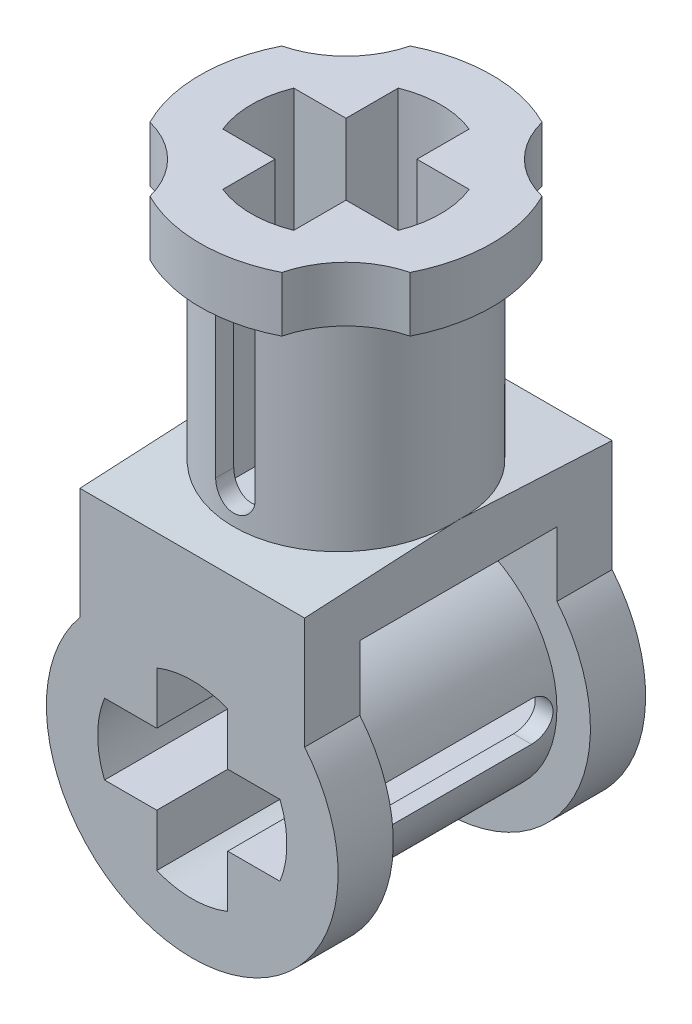
SolidWorks part; units mm, degrees
ref_plane "Front Plane" through (0, 0, 0) normal (0, 0, 1) x (1, 0, 0)
ref_plane "Top Plane" through (0, 0, 0) normal (0, 1, 0) x (1, 0, 0)
ref_plane "Right Plane" through (0, 0, 0) normal (1, 0, 0) x (0, 0, -1)
sketch "Sketch1" plane through (0, 0, 0) normal (0, 1, 0) x (1, 0, 0)
  circle A0 centre (0, 0) radius 2.85
  dimension "D1" = 5.7
extrude "Middle Body" add sketch "Sketch1" along normal mid plane 5.1
sketch "Sketch2" plane through (0, -2.55, 0) normal (0, -1, 0) x (1, 0, 0)
  circle A0 centre (0, 0) radius 3.7
  dimension "D1" = 7.4
extrude "Outer Rim" add sketch "Sketch2" along normal blind 1.4
mirror "Mirror1" about plane through (0, 0, 0) normal (0, 1, 0) of "Outer Rim"
sketch "Sketch3" plane through (0, 0, 0) normal (0, 1, 0) x (1, 0, 0)
  line L1 (2.4, -0.9) -> (-2.4, -0.9)
  line L2 (2.4, -0.9) -> (2.4, 0.9)
  line L3 (2.4, 0.9) -> (-2.4, 0.9)
  line L4 (-2.4, -0.9) -> (-2.4, 0.9)
  line L5 (2.4, -0.9) -> (-2.4, 0.9) construction
  line L6 (2.4, 0.9) -> (-2.4, -0.9) construction
  line L7 (0.9, -2.4) -> (-0.9, -2.4)
  line L8 (0.9, -2.4) -> (0.9, 2.4)
  line L9 (0.9, 2.4) -> (-0.9, 2.4)
  line L10 (-0.9, -2.4) -> (-0.9, 2.4)
  line L11 (0.9, -2.4) -> (-0.9, 2.4) construction
  line L12 (0.9, 2.4) -> (-0.9, -2.4) construction
  circle A0 centre (0, 0) radius 2.4
  dimension "D1" = 4.8
  dimension "D2" = 1.8
extrude "Axle Cut" cut sketch "Sketch3" against normal through all both and the other way through all contours L8 A0 L10 L3 | L3 A0 L1 L10 | L10 L1 L8 L3 | A0 L8 L1 L10 | L1 A0 L3 L8 region at (1.6222, 0, 0) region at (0, 0, 1.6222) region at (0, 0, 0) region at (-1.6222, 0, 0) region at (0, 0, -1.6222)
sketch "Sketch4" plane through (0, 0, 0) normal (0, 0, 1) x (1, 0, 0)
  line L0 (0, -1.9) -> (0, 1.9) construction
  line L1 (-0.5, -1.9) -> (-0.5, 1.9)
  line L2 (0.5, -1.9) -> (0.5, 1.9)
  arc A0 (-0.5, -1.9) -> (0.5, -1.9) centre (0, -1.9) ccw
  arc A1 (0.5, 1.9) -> (-0.5, 1.9) centre (0, 1.9) ccw
  point P2 (0, 0)
  dimension "D2" = 4.8
  dimension "D1" = 1
extrude "Slot Cut" cut sketch "Sketch4" against normal through all both and the other way through all
sketch "Sketch5" plane through (0, 3.95, 0) normal (0, 1, 0) x (1, 0, 0)
  line L0 (0, 0) -> (3.8509, 3.8509) construction
  line L2 (0.9, 0.9) -> (0.9, 2.2249) construction
  circle A0 centre (0, 0) radius 3.2
  circle A3 centre (3.8509, 3.8509) radius 2.246
  circle A4 centre (0, 0) radius 3.7 construction
  circle A5 centre (3.8509, -3.8509) radius 2.246
  circle A6 centre (-3.8509, -3.8509) radius 2.246
  circle A7 centre (-3.8509, 3.8509) radius 2.246
  point P7 (1.6735, 3.2999)
  point P8 (3.2999, 1.6735)
  circle M23 centre (0, 0) radius 3.7
  dimension "D1" = 6.4
  dimension "D3" = 2.3
  dimension "D2" = 45
  dimension "D4" = 4
extrude "Scallop Cut " cut sketch "Sketch5" against normal blind 1.4 contours A7 M23 | L0 A3 M23 | A3 L0 M23 | A5 | A6 region at (2.141, 3.95, -2.7556) region at (2.7556, 3.95, -2.141) region at (-2.4483, 3.95, -2.4483)
sketch "Sketch6" plane through (0, 0, 0) normal (0, 0, 1) x (1, 0, 0)
  line L0 (1.6735, 3.95) -> (-1.6735, 3.95) construction
  circle A0 centre (0, -7.95) radius 2.85
  dimension "D1" = 5.7
  dimension "D2" = 11.9
extrude "Middle Top " add sketch "Sketch6" along normal mid plane 7.8 separate body
sketch "Sketch7" plane through (0, 0, 3.9) normal (0, 0, 1) x (1, 0, 0)
  circle A0 centre (0, -7.95) radius 3.7
  point P2 (0, -7.95)
  dimension "D1" = 7.4
extrude "Top Rim " add sketch "Sketch7" against normal blind 1.4
mirror "Mirror2" about plane through (0, 0, 0) normal (0, 0, 1) of "Top Rim "
sketch "Sketch8" plane through (0, 0, 0) normal (1, 0, 0) x (0, 0, -1)
  line L0 (3.9, -2.55) -> (-3.9, -2.55)
  line L1 (3.7, -2.55) -> (-3.7, -2.55) construction
  line L2 (-3.9, -2.55) -> (-3.9, -6.1)
  line L3 (-3.9, -4.25) -> (-3.9, -11.65) construction
  line L4 (-3.9, -6.1) -> (-2.5, -6.1)
  line L5 (-2.5, -10.8) -> (-2.5, -5.1) construction
  line L6 (-2.5, -6.1) -> (-2.5, -3.95)
  line L7 (-3.7, -3.95) -> (3.7, -3.95) construction
  line L8 (-2.5, -3.95) -> (2.5, -3.95)
  line L9 (0, -3.95) -> (0, -2.55) construction
  line L10 (2.5, -5.1) -> (-2.5, -5.1) construction
  line L11 (2.5, -6.1) -> (2.5, -3.95)
  line L12 (3.9, -6.1) -> (2.5, -6.1)
  line L13 (3.9, -2.55) -> (3.9, -6.1)
  dimension "D1" = 1
extrude "Axle Joint " add sketch "Sketch8" along normal mid plane 5.7
sketch "Sketch9" plane through (2.85, 0, 0) normal (1, 0, 0) x (0, 0, -1)
  line L1 (3.9, -2.55) -> (-3.9, -2.55)
  line L2 (3.9, -2.55) -> (3.9, -5.5904)
  line L3 (3.9, -5.5904) -> (-3.9, -5.5904)
  line L4 (-3.9, -2.55) -> (-3.9, -5.5904)
extrude "Side Cut " cut sketch "Sketch9" along normal blind 5.7
mirror "Mirror3" about plane through (0, 0, 0) normal (1, 0, 0) of "Side Cut "
sketch "Sketch10" plane through (0, 0, 0) normal (1, 0, 0) x (0, 0, -1)
  line L1 (2.5, -3.95) -> (-2.5, -3.95)
  line L2 (2.5, -3.95) -> (2.5, -5.5904)
  line L3 (2.5, -5.5904) -> (-2.5, -5.5904)
  line L4 (-2.5, -3.95) -> (-2.5, -5.5904)
extrude "MIddle Wall " add sketch "Sketch10" along normal mid plane 1.4
draft "Draft1" type of draft neutral plane draft angle 3 neutral plane "Front Plane" faces to draft 1 face at (0, -2.55, 2.6625) neutral plane through (0, 0, 0) neutral plane normal (0, 0, 1) parameters "D1"=3
draft "Draft2" type of draft neutral plane draft angle 3 neutral plane "Front Plane" faces to draft 1 face at (0, -2.55, -2.6625) neutral plane through (0, 0, 0) neutral plane normal (0, 0, 1) reverse direction yes parameters "D1"=3
sketch "Sketch11" plane through (0, 0, 0) normal (0, 0, 1) x (1, 0, 0)
  line L1 (0.9, -10.35) -> (-0.9, -10.35)
  line L2 (0.9, -10.35) -> (0.9, -5.55)
  line L3 (0.9, -5.55) -> (-0.9, -5.55)
  line L4 (-0.9, -10.35) -> (-0.9, -5.55)
  line L5 (0.9, -10.35) -> (-0.9, -5.55) construction
  line L6 (0.9, -5.55) -> (-0.9, -10.35) construction
  line L7 (2.4, -8.85) -> (-2.4, -8.85)
  line L8 (2.4, -8.85) -> (2.4, -7.05)
  line L9 (2.4, -7.05) -> (-2.4, -7.05)
  line L10 (-2.4, -8.85) -> (-2.4, -7.05)
  line L11 (2.4, -8.85) -> (-2.4, -7.05) construction
  line L12 (2.4, -7.05) -> (-2.4, -8.85) construction
  circle A0 centre (0, -7.95) radius 2.4
  dimension "D1" = 4.8
  dimension "D2" = 1.8
extrude "Axle Cut " cut sketch "Sketch11" against normal through all both and the other way through all contours L9 A0 L7 L4 | L2 L9 L4 L7 | L2 A0 L4 L9 | A0 L9 L2 L7 | L4 A0 L2 L7 region at (0, -9.5722, 0) region at (0, -7.95, 0) region at (1.6222, -7.95, 0) region at (-1.6222, -7.95, 0) region at (0, -6.3278, 0)
sketch "Sketch12" plane through (0, 0, 0) normal (1, 0, 0) x (0, 0, -1)
  line L0 (-1.9, -7.95) -> (1.9, -7.95) construction
  line L1 (-1.9, -7.45) -> (1.9, -7.45)
  line L2 (-1.9, -8.45) -> (1.9, -8.45)
  line L3 (1.6735, 3.95) -> (-1.6735, 3.95) construction
  arc A0 (-1.9, -7.45) -> (-1.9, -8.45) centre (-1.9, -7.95) ccw
  arc A1 (1.9, -8.45) -> (1.9, -7.45) centre (1.9, -7.95) ccw
  point P2 (0, -7.95)
  point P7 (0, 0)
  dimension "D1" = 1
  dimension "D2" = 3.8
  dimension "D3" = 11.9
extrude "Top Slot " cut sketch "Sketch12" against normal through all both and the other way through all
